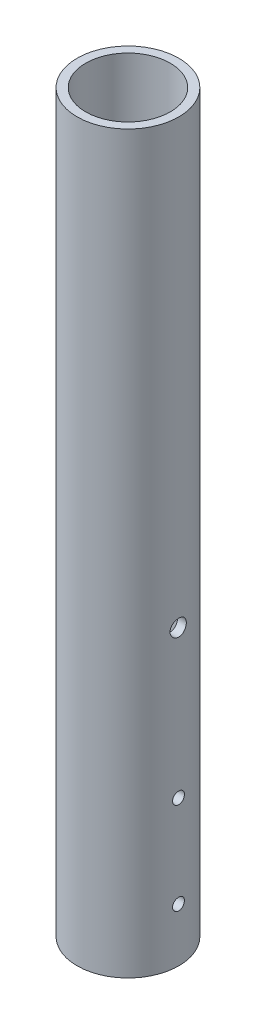
SolidWorks part; units mm, degrees
material "6061 Alloy"
ref_plane "Front Plane" through (0, 0, 0) normal (0, 0, 1) x (1, 0, 0)
ref_plane "Top Plane" through (0, 0, 0) normal (0, 1, 0) x (1, 0, 0)
ref_plane "Right Plane" through (0, 0, 0) normal (1, 0, 0) x (0, 0, -1)
sketch "Sketch1" plane through (0, 0, 0) normal (0, 1, 0) x (1, 0, 0)
  circle A0 centre (0, 0) radius 21.082
  circle A1 centre (0, 0) radius 17.526
  dimension "D1" = 42.164
  dimension "D2" = 35.052
extrude "Boss-Extrude1" add sketch "Sketch1" along normal blind 304.8
ref_plane "Plane1" through (-21.082, 0, 0) normal (-1, 0, 0) x (0, 0, 1)
hole_wizard "#10 (0.1935) Diameter Hole1" positions "Sketch2" profile "Sketch3" hole size "#10" standard "ANSI Inch" end condition through all
sketch "Sketch2" plane through (-21.082, 0, 0) normal (-1, 0, 0) x (0, 0, 1)
  line L0 (0, 0) -> (0, 304.8) construction
  line L1 (17.526, 304.8) -> (-17.526, 304.8) construction
  line L2 (-21.082, 0) -> (21.082, 0) construction
  point P0 (0, 22.225)
  point P2 (0, 60.325)
  dimension "D1" = 38.1
  dimension "D2" = 22.225
sketch "Sketch3" plane through (-21.082, 22.225, 0) normal (0, 1, 0) x (0, 0, 1)
  line L0 (0, 0) -> (0, 42.164)
  line L1 (0, 42.164) -> (2.4574, 42.164)
  line L2 (2.4574, 42.164) -> (2.4574, 0)
  line L5 (2.4574, 0) -> (0, 0)
  line L11 (0, -6.35) -> (0, 107.95) construction
  dimension "Thru Hole Dia." = 4.9149
  dimension "Thru Hole Depth" = 42.164
hole_wizard "1/4 Clearance Hole1" positions "Sketch4" profile "Sketch5" hole size "1/4" standard "ANSI Inch" end condition through all
sketch "Sketch4" plane through (-21.082, 0, 0) normal (1, 0, 0) x (0, 0, -1)
  line L0 (0, 304.8) -> (0, 0) construction
  line L1 (17.526, 304.8) -> (-17.526, 304.8) construction
  line L4 (-3.2079, 127) -> (-6.4158, 121.4438) construction
  line L5 (-6.4158, 121.4438) -> (-3.2079, 115.8875) construction
  line L6 (-3.2079, 115.8875) -> (3.2079, 115.8875) construction
  line L7 (3.2079, 115.8875) -> (6.4158, 121.4437) construction
  line L8 (6.4158, 121.4437) -> (3.2079, 127) construction
  line L9 (3.2079, 127) -> (-3.2079, 127) construction
  line L10 (-21.082, 127) -> (21.082, 127) construction
  line L11 (-21.082, 304.8) -> (-21.082, 0) construction
  line L12 (21.082, 0) -> (21.082, 304.8) construction
  line L13 (-21.082, 0) -> (21.082, 0) construction
  circle A0 centre (0, 121.4438) radius 3.175 construction
  circle A1 centre (0, 121.4438) radius 5.5563 construction
  point P0 (0, 121.4438)
  dimension "D1" = 6.35
  dimension "D2" = 11.1125
  dimension "D3" = 127
  dimension "D4" = 121.4438
sketch "Sketch5" plane through (-21.082, 121.4438, 0) normal (0, 1, 0) x (0, 0, 1)
  line L0 (0, 0) -> (0, 42.164)
  line L1 (0, 42.164) -> (3.3782, 42.164)
  line L2 (3.3782, 42.164) -> (3.3782, 0)
  line L5 (3.3782, 0) -> (0, 0)
  line L11 (0, -6.35) -> (0, 107.95) construction
  dimension "Thru Hole Dia." = 6.7564
  dimension "Thru Hole Depth" = 42.164
